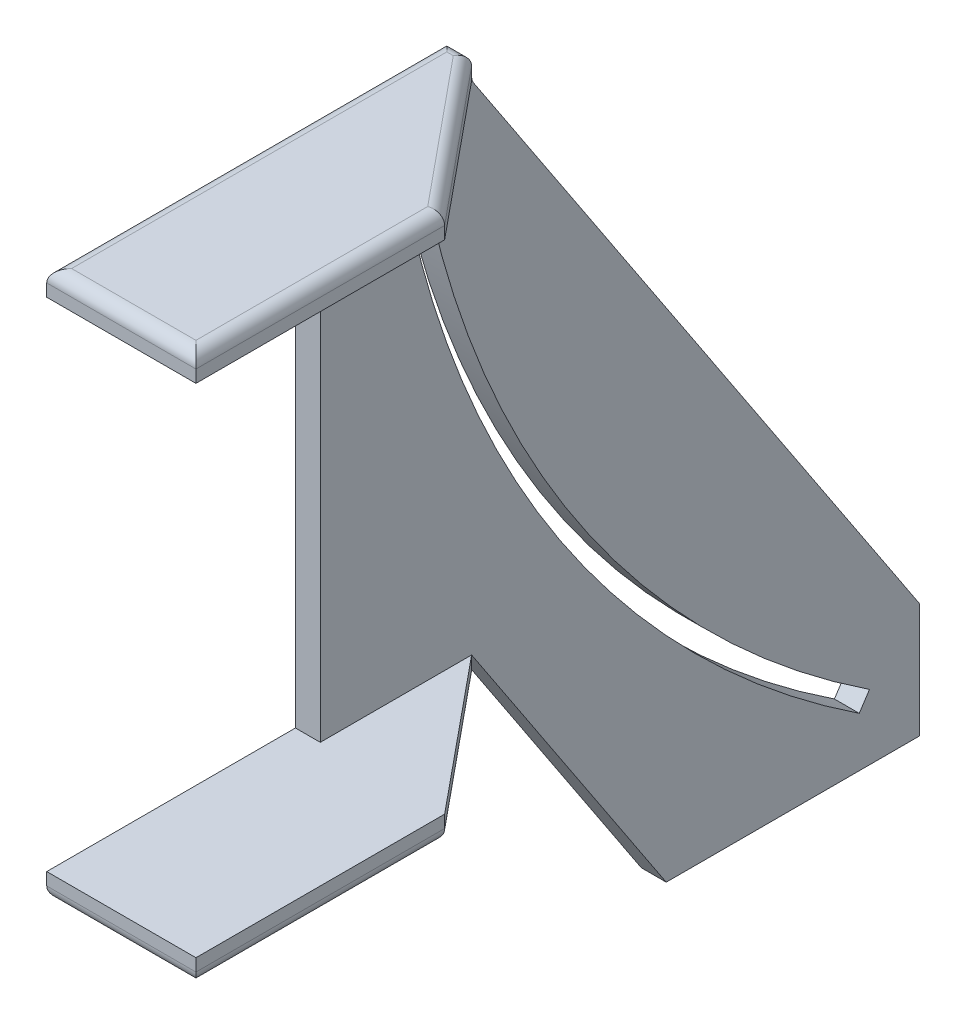
SolidWorks part; units mm, degrees
ref_plane "Front Plane" through (0, 0, 0) normal (0, 0, 1) x (1, 0, 0)
ref_plane "Top Plane" through (0, 0, 0) normal (0, 1, 0) x (1, 0, 0)
ref_plane "Right Plane" through (0, 0, 0) normal (1, 0, 0) x (0, 0, -1)
sketch "Sketch1" plane through (0, 0, 0) normal (1, 0, 0) x (0, 0, -1)
  line L0 (-132.3245, -23.876) -> (-129.9041, -23.876)
  line L1 (-74.0657, -112.2234) -> (-72.7541, -110.236)
  line L2 (-123.5541, -17.526) -> (-66.4041, -103.886)
  line L3 (-142.875, -17.526) -> (-123.5541, -17.526)
  line L4 (-142.875, -17.526) -> (-142.875, -81.026)
  line L5 (-98.7065, -118.5734) -> (-66.4041, -118.5734)
  line L6 (-66.4041, -103.886) -> (-66.4041, -118.5734)
  line L7 (-142.875, -81.026) -> (-123.5541, -81.026)
  line L8 (-123.5541, -81.026) -> (-98.7065, -118.5734)
  arc A0 (-129.9041, -23.876) -> (-72.7541, -110.236) centre (0, 0) ccw
  arc A1 (-132.3245, -23.876) -> (-74.0657, -112.2234) centre (0, 0) ccw
  point P2 (-123.5541, -83.1641)
  point P11 (-117.5825, -81.026)
  point P14 (-131.1143, -23.876)
  point P15 (-123.5541, -81.026)
  dimension "D1" = 132.08
  dimension "D2" = 2.3813
  dimension "D3" = 142.875
  dimension "D4" = 6.35
  dimension "D5" = 6.35
  dimension "D6" = 6.35
  dimension "D7" = 6.35
  dimension "D8" = 6.35
  dimension "D9" = 57.15
  dimension "D10" = 17.526
  dimension "D11" = 0
  dimension "D12" = 63.5
extrude "Boss-Extrude1" add sketch "Sketch1" along normal blind 3.175
sketch "Sketch2" plane through (0, -17.526, 0) normal (0, 1, 0) x (1, 0, 0)
  line L0 (3.175, -142.875) -> (0, -142.875) construction
  line L1 (0, -123.5541) -> (3.175, -123.5541)
  line L2 (0, -123.5541) -> (0, -174.625)
  line L3 (0, -174.625) -> (19.05, -174.625)
  line L4 (19.05, -142.875) -> (19.05, -174.625)
  line L5 (3.175, -123.5541) -> (19.05, -142.875)
  point P8 (1.5875, -142.875)
  dimension "D1" = 31.75
  dimension "D2" = 19.05
  dimension "D3" = 0
extrude "Boss-Extrude2" add sketch "Sketch2" along normal blind 3.175
fillet "Fillet1" radius 1.5875 6 edges at (1.5875, -14.351, 123.5541) (0, -14.351, 149.0895) (9.525, -14.351, 174.625) (19.05, -14.351, 158.75) (11.1125, -14.351, 133.2145) (1.5875, -17.526, 123.5541)
sketch "Sketch4" plane through (0, -81.026, 0) normal (0, -1, 0) x (1, 0, 0)
  line L0 (0, 123.5541) -> (3.175, 123.5541)
  line L1 (3.175, 123.5541) -> (19.05, 142.875)
  line L2 (19.05, 142.875) -> (19.05, 174.625)
  line L3 (19.05, 174.625) -> (0, 174.625)
  line L4 (0, 174.625) -> (0, 123.5541)
extrude "Boss-Extrude3" add sketch "Sketch4" along normal blind 3.175
fillet "Fillet2" radius 1.5875 5 edges at (9.525, -84.201, 174.625) (19.05, -84.201, 158.75) (11.1125, -84.201, 133.2145) (1.5875, -84.201, 123.5541) (0, -84.201, 149.0895)
